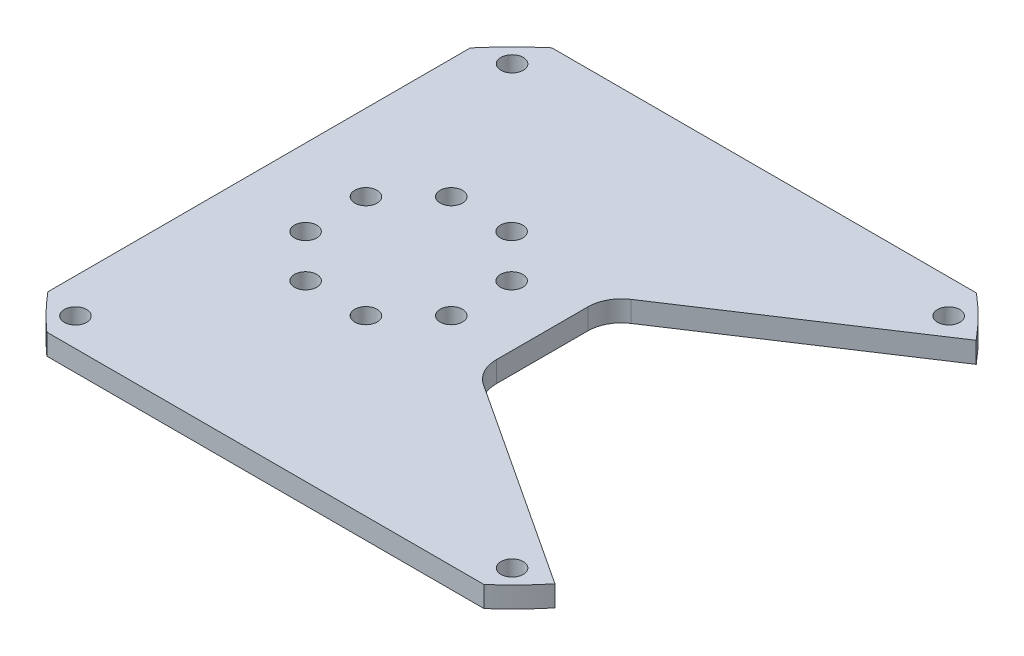
SolidWorks part; units mm, degrees
ref_plane "Front Plane" through (0, 0, 0) normal (0, 0, 1) x (1, 0, 0)
ref_plane "Top Plane" through (0, 0, 0) normal (0, 1, 0) x (1, 0, 0)
ref_plane "Right Plane" through (0, 0, 0) normal (1, 0, 0) x (0, 0, -1)
sketch "Sketch1" plane through (0, 0, 0) normal (0, 1, 0) x (1, 0, 0)
  line L0 (-38.5095, 32.1488) -> (-38.5095, -32.1488)
  line L1 (-33.2269, 33.2269) -> (33.2269, 33.2269) construction
  line L2 (-33.2269, 33.2269) -> (-33.2269, -33.2269) construction
  line L3 (-33.2269, -33.2269) -> (33.2269, -33.2269) construction
  line L4 (33.2269, 33.2269) -> (33.2269, -33.2269) construction
  line L5 (-33.2269, 33.2269) -> (33.2269, -33.2269) construction
  line L6 (-33.2269, -33.2269) -> (33.2269, 33.2269) construction
  line L13 (-33.274, -37.5416) -> (33.274, -37.5416)
  line L14 (-32.3186, 38.3671) -> (32.3186, 38.3671)
  line L15 (4.572, 9.721) -> (4.572, -9.721)
  line L16 (4.572, -9.721) -> (38.5873, -32.0554)
  line L17 (4.572, 9.721) -> (38.5414, 32.1106)
  circle A0 centre (0, 0) radius 50.165 construction
  arc A2 (38.5873, -32.0554) -> (33.274, -37.5416) centre (0, 0) cw
  arc A3 (38.5414, 32.1106) -> (32.3186, 38.3671) centre (0, 0) ccw
  arc A4 (-32.3186, 38.3671) -> (-38.5095, 32.1488) centre (0, 0) ccw
  arc A5 (-33.274, -37.5416) -> (-38.5095, -32.1488) centre (0, 0) cw
  circle A6 centre (-15.748, 0) radius 12 construction
  point P3 (-15.748, 0)
  point P15 (4.572, 0)
  point P22 (-4.6614, -4.5922)
  point P24 (-15.748, 0)
  dimension "D1" = 100.33
  dimension "D2" = 24
  dimension "D3" = 22.5
  dimension "D4" = 93.98
extrude "Boss-Extrude1" add sketch "Sketch1" along normal mid plane 3.175
hole_wizard "M3 Clearance Hole1" positions "Sketch2" profile "Sketch3" hole size "M3" standard "ISO" end condition through all
sketch "Sketch2" plane through (0, 1.5875, 0) normal (0, 1, 0) x (1, 0, 0)
  point P0 (-33.2269, 33.2269)
  point P3 (33.2269, 33.2269)
  point P6 (33.2269, -33.2269)
  point P9 (-33.2269, -33.2269)
sketch "Sketch3" plane through (-33.2269, 1.5875, -33.2269) normal (1, 0, 0) x (0, 0, 1)
  line L0 (0, 0) -> (0, 3.175)
  line L1 (0, 3.175) -> (1.7, 3.175)
  line L2 (1.7, 3.175) -> (1.7, 0)
  line L5 (1.7, 0) -> (0, 0)
  line L11 (0, -6.35) -> (0, 107.95) construction
  dimension "Thru Hole Dia." = 3.4
  dimension "Thru Hole Depth" = 3.175
hole_wizard "M3 Clearance Hole2" positions "Sketch4" profile "Sketch5" hole size "M3" standard "ISO" end condition through all
sketch "Sketch4" plane through (0, -1.5875, 0) normal (0, -1, 0) x (-1, 0, 0)
  point P0 (4.6614, -4.5922)
sketch "Sketch5" plane through (-4.6614, -1.5875, 4.5922) normal (1, 0, 0) x (0, 0, -1)
  line L0 (0, 0) -> (0, 3.175)
  line L1 (0, 3.175) -> (1.7, 3.175)
  line L2 (1.7, 3.175) -> (1.7, 0)
  line L5 (1.7, 0) -> (0, 0)
  line L11 (0, -6.35) -> (0, 107.95) construction
  dimension "Thru Hole Dia." = 3.4
  dimension "Thru Hole Depth" = 3.175
ref_axis "Axis1" through (-15.748, 0, 0) along (0, -1, 0)
pattern_circular "CirPattern1" count 8 every 45 about axis through (-15.748, 0, 0) along (0, -1, 0) of "M3 Clearance Hole2"
fillet "Fillet1" radius 5.08 2 edges at (4.572, 0, -9.721) (4.572, 0, 9.721)
